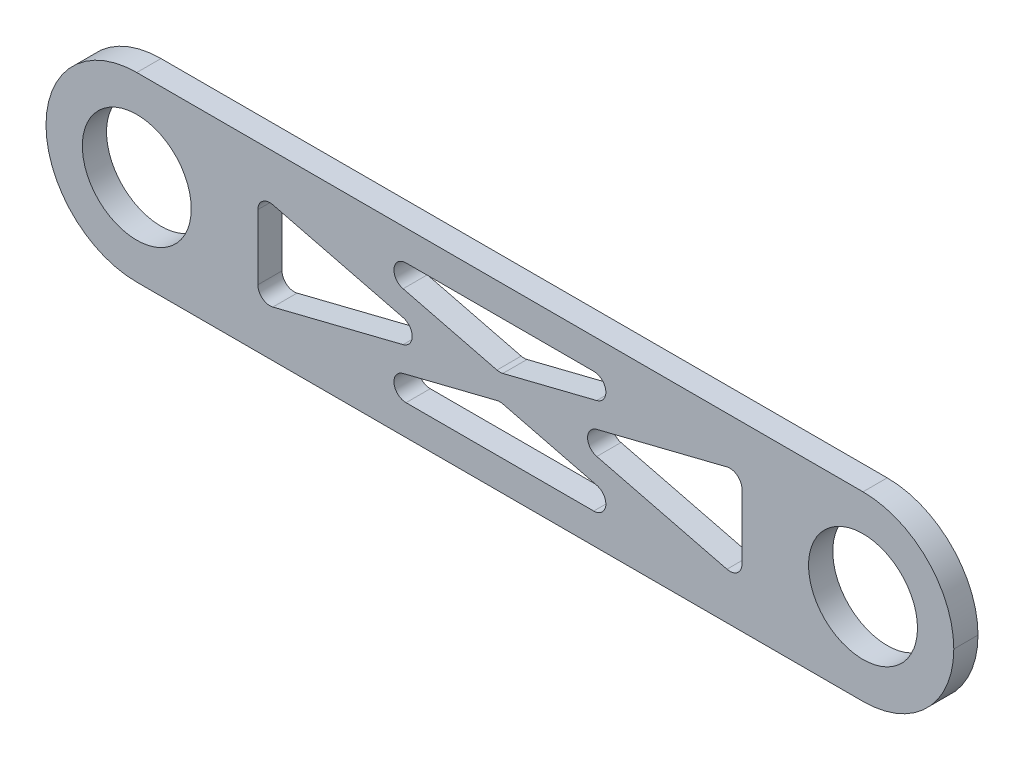
SolidWorks part; units mm, degrees
material "Thornel Mat VMA"
ref_plane "前视基准面" through (0, 0, 0) normal (0, 0, 1) x (1, 0, 0)
ref_plane "上视基准面" through (0, 0, 0) normal (0, 1, 0) x (1, 0, 0)
ref_plane "右视基准面" through (0, 0, 0) normal (1, 0, 0) x (0, 0, -1)
sketch "草图1" plane through (0, 0, 0) normal (0, 0, 1) x (1, 0, 0)
  line L1 (-37.5, -7.5) -> (37.5, -7.5)
  line L2 (-37.5, -7.5) -> (-37.5, 7.5)
  line L3 (-37.5, 7.5) -> (37.5, 7.5)
  line L4 (37.5, -7.5) -> (37.5, 7.5)
  line L5 (-37.5, -7.5) -> (37.5, 7.5) construction
  line L6 (-37.5, 7.5) -> (37.5, -7.5) construction
  point P0 (0, 0)
  dimension "D1" = 75
  dimension "D2" = 15
extrude "凸台-拉伸1" add sketch "草图1" along normal blind 2
fillet "圆角1" radius 7.5 4 edges at (37.5, -7.5, 1) (-37.5, -7.5, 1) (-37.5, 7.5, 1) (37.5, 7.5, 1)
sketch "草图2" plane through (0, 0, 2) normal (0, 0, 1) x (1, 0, 0)
  circle A0 centre (30, 0) radius 4.5
  circle A1 centre (-30, 0) radius 4.5
  dimension "D1" = 9
  dimension "D2" = 9
extrude "切除-拉伸1" cut sketch "草图2" against normal blind 2
sketch "草图3" plane through (0, 0, 2) normal (0, 0, 1) x (1, 0, 0)
  line L0 (-15.8769, -5) -> (0, -1.0308)
  line L1 (-15.8769, -5) -> (20, -5)
  line L2 (-20, -3.9692) -> (-20, 3.9692)
  line L3 (-15.8769, 5) -> (15.8769, 5)
  line L4 (20, -5) -> (20, 3.9692)
  line L5 (-20, -5) -> (20, 5) construction
  line L6 (-20, 5) -> (20, -5) construction
  line L7 (-20, 3.9692) -> (-4.1231, 0)
  line L8 (-20, -3.9692) -> (-4.1231, 0)
  line L9 (-15.8769, 5) -> (0, 1.0308)
  line L10 (4.1231, 0) -> (20, -3.9692)
  line L11 (-20.2425, 4.0299) -> (19.7575, -5.9701) construction
  line L12 (-19.7575, 5.9701) -> (20.2425, -4.0299) construction
  line L13 (-20.2425, -4.0299) -> (19.7575, 5.9701) construction
  line L14 (-19.7575, -5.9701) -> (20.2425, 4.0299) construction
  line L15 (4.1231, 0) -> (20, 3.9692)
  line L16 (0, -1.0308) -> (15.8769, -5)
  line L17 (0, 1.0308) -> (15.8769, 5)
  point P0 (0, 0)
  dimension "D1" = 40
  dimension "D2" = 10
  dimension "D3" = 1
  dimension "D4" = 1
extrude "切除-拉伸2" cut sketch "草图3" against normal blind 10 contours L2 L8 L7 | L9 L17 L3 | L16 L0 L1 | L15 L10 L4 region at (14.7077, 0, 2) region at (0, -3.6769, 2) region at (-14.7077, 0, 2) region at (0, 3.6769, 2)
fillet "圆角2" radius 1 12 edges at (-15.8769, -5, 1) (0, -1.0308, 1) (15.8769, -5, 1) (20, -3.9692, 1) (4.1231, 0, 1) (20, 3.9692, 1) (-4.1231, 0, 1) (-20, 3.9692, 1) (-15.8769, 5, 1) (15.8769, 5, 1) (0, 1.0308, 1) (-20, -3.9692, 1)
